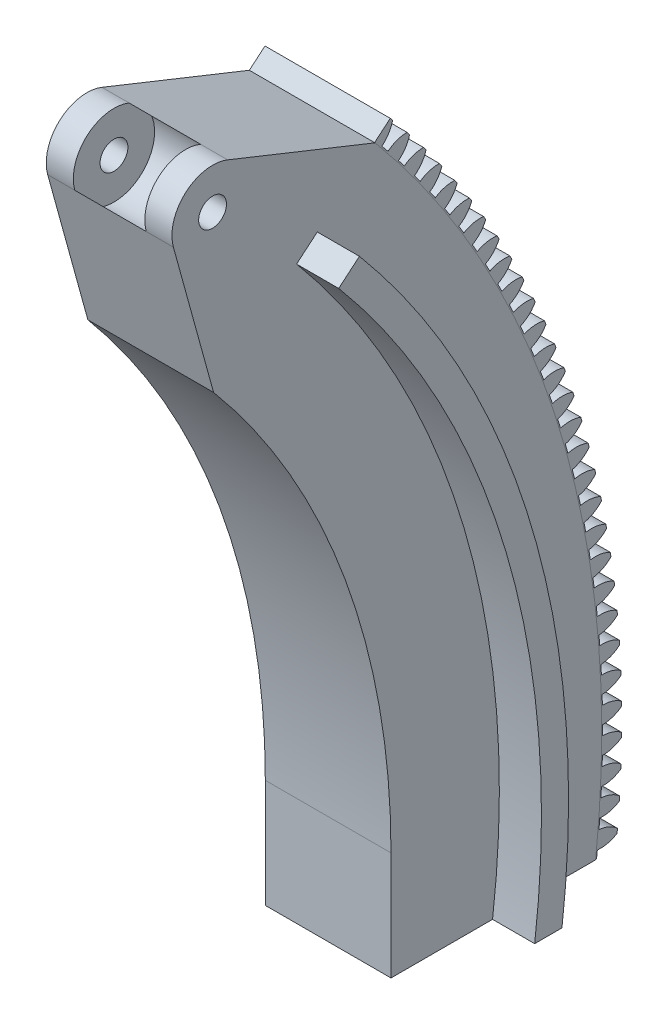
SolidWorks part; units mm, degrees
material "ABS"
ref_plane "Front Plane" through (0, 0, 0) normal (0, 0, 1) x (1, 0, 0)
ref_plane "Top Plane" through (0, 0, 0) normal (0, 1, 0) x (1, 0, 0)
ref_plane "Right Plane" through (0, 0, 0) normal (1, 0, 0) x (0, 0, -1)
ref_plane "Plane2" through (6.35, 0, 0) normal (1, 0, 0) x (0, 0, -1)
sketch "Sketch1" plane through (0, 0, 0) normal (1, 0, 0) x (0, 0, -1)
  line L0 (-1000, 0) -> (177.8, 0) construction
  line L1 (177.8, 0) -> (177.8, -25.4)
  line L2 (0, 0) -> (136.2027, 114.2876) construction
  line L4 (227.2, 0) -> (49000, 0) construction
  line L7 (177.8, -25.4) -> (227.2, -25.4) construction
  line L8 (227.2, 0) -> (227.2, -25.4) construction
  line L10 (-1.0719, -0.8495) -> (179.1555, 141.9904) construction
  line L61 (181.0098, 139.6187) -> (0, 0) construction
  line L62 (136.2027, 114.2876) -> (126.7844, 148.4774)
  line L64 (177.8, -25.4) -> (225.7757, -25.4)
  line L65 (136.2027, 114.2876) -> (155.124, 130.1645) construction
  line L66 (155.124, 130.1645) -> (174.0453, 146.0413) construction
  line L68 (0, 0) -> (35966.99, 34732.9185) construction
  line L69 (178.0587, 141.1212) -> (178.0836, 141.1409) construction
  line L70 (0, 0) -> (135.9673, 151.007) construction
  line L71 (139.5033, 159.8514) -> (174.0453, 146.0413)
  arc A2 (177.8, 0) -> (136.2027, 114.2876) centre (0, 0) ccw
  circle A19 centre (0, 0) radius 228.6 construction
  arc A22 (174.0453, 146.0413) -> (227.2, 0) centre (0, 0) cw
  arc A23 (227.2, 0) -> (225.7757, -25.4) centre (0, 0) cw
  arc A24 (126.7844, 148.4774) -> (139.5033, 159.8514) centre (135.9673, 151.007) cw
  point P6 (178.0836, 141.1409)
  point P7 (136.2027, 114.2876)
  dimension "D1" = 177.8
  dimension "D2" = 6.35
  dimension "D12" = 457.2
  dimension "D8" = 9.525
  dimension "D3" = 40
  dimension "D4" = 49.4
  dimension "D5" = 25.4
  dimension "D6" = 203.2
  dimension "D7" = 48
  dimension "D13" = 44
sketch "Sketch2" plane through (6.35, 0, 0) normal (1, 0, 0) x (0, 0, -1)
  line L0 (0, 0) -> (165.1, 0) construction
  line L1 (165.1, 0) -> (190.5, 0) construction
  line L2 (0, 0) -> (49240.3877, 8682.4089) construction
  circle A0 centre (165.1, 0) radius 3.2639
  circle A1 centre (190.5, 0) radius 3.2639
  arc A3 (165.1, 0) -> (162.5918, 28.6693) centre (0, 0) ccw construction
  circle A4 centre (162.5918, 28.6693) radius 3.2639
  arc A5 (190.5, 0) -> (187.6059, 33.08) centre (0, 0) ccw construction
  circle A6 centre (187.6059, 33.08) radius 3.2639
  dimension "D3" = 6.5278
  dimension "D4" = 6.5278
  dimension "D6" = 6.5278
  dimension "D7" = 6.5278
  dimension "D1" = 165.1
  dimension "D2" = 25.4
  dimension "D5" = 10
sketch "Sketch11" plane through (6.35, 0, 0) normal (1, 0, 0) x (0, 0, -1)
  line L0 (-785.502, -659.1144) -> (0, 0) construction
  line L2 (-1000, 0) -> (0, 0) construction
  line L4 (155.6602, 130.6144) -> (177.7223, 149.1267)
  line L5 (177.7223, 149.1267) -> (921.7047, 773.4021) construction
  line L6 (232, 0) -> (232, -25.4) construction
  line L7 (232, -25.4) -> (222.9391, -25.4) construction
  line L8 (201.6062, -25.4) -> (230.6054, -25.4)
  line L9 (203.2, 0) -> (232, 0) construction
  arc A0 (-230, 0) -> (-176.1902, -147.8412) centre (0, 0) ccw construction
  arc A1 (-232, 0) -> (-177.7223, -149.1267) centre (0, 0) ccw construction
  arc A2 (-229.6, 0) -> (-175.8838, -147.584) centre (0, 0) ccw construction
  arc A3 (232, 0) -> (177.7223, 149.1267) centre (0, 0) ccw
  arc A4 (230, 0) -> (176.1902, 147.8412) centre (0, 0) ccw construction
  arc A5 (-229.6, 0) -> (-175.8838, -147.584) centre (0, 0) ccw
  arc A6 (155.6602, 130.6144) -> (203.2, 0) centre (0, 0) cw
  arc A7 (232, 0) -> (230.6054, -25.4) centre (0, 0) cw
  arc A8 (203.2, 0) -> (201.6062, -25.4) centre (0, 0) cw
  dimension "D1" = 460
  dimension "D2" = 464
  dimension "D4" = 203.2
  dimension "D3" = 2.4
  dimension "D6" = 25.4
extrude "Boss-Extrude2" add sketch "Sketch11" against normal blind 6.35 contours A3 L4 region at (6.35, 60.7212, -203.0048)
sketch "Sketch12" plane through (6.35, 0, 0) normal (1, 0, 0) x (0, 0, -1)
  line L0 (0, 0) -> (232, 0) construction
  line L2 (229.9946, 1.5708) -> (229.9946, -1.5708) construction
  line L3 (0, 0) -> (227.4972, 1.1241) construction
  line L4 (225.6789, 0) -> (232.9848, 2.6591) construction
  line L5 (0, 0) -> (232.9783, 3.1825) construction
  line L6 (229.9946, 1.5708) -> (229.9517, 4.7121) construction
  circle A0 centre (0, 0) radius 230 construction
  arc A1 (230.6054, -25.4) -> (177.7223, 149.1267) centre (0, 0) ccw construction
  circle A2 centre (0, 0) radius 227.5 construction
  arc A3 (227.4972, 1.1241) -> (232.9725, 3.5819) centre (227.4606, 8.5329) ccw
  arc A4 (231.5994, -25.5095) -> (232.9725, -3.5819) centre (0, 0) cw construction
  arc A5 (227.4972, -1.1241) -> (232.9725, -3.5819) centre (227.4606, -8.5329) cw
  arc A6 (231.5994, -25.5095) -> (178.4884, 149.7695) centre (0, 0) ccw
  arc A7 (231.5994, -25.5095) -> (232.9725, 3.5819) centre (0, 0) ccw construction
  arc A8 (227.4972, 1.1241) -> (227.4972, -1.1241) centre (0, 0) cw
  arc A9 (230.6054, -25.4) -> (177.7223, 149.1267) centre (0, 0) ccw construction
  arc A10 (232.9725, 3.5819) -> (232.9725, -3.5819) centre (0, 0) cw
  dimension "D1" = 460
  dimension "D3" = 20
  dimension "D4" = 0.783
  dimension "D5" = 4.5
  dimension "D2" = 1
extrude "Boss-Extrude3" add sketch "Sketch1" along normal blind 29.464
extrude "Cut-Extrude4" cut sketch "Sketch12" against normal blind 6.35
pattern_circular "CirPattern3" count 230 every 1.565 about axis through (0, 0, 0) along (1, 0, 0) of "Cut-Extrude4"
sketch "Sketch15" plane through (6.35, 0, 0) normal (1, 0, 0) x (0, 0, -1)
  line L0 (0, 0) -> (135.9673, 151.007) construction
  line L2 (0, 0) -> (102.4673, 0) construction
  circle A0 centre (135.9673, 151.007) radius 3.2639
  dimension "D3" = 6.5278
  dimension "D1" = 203.2
  dimension "D2" = 48
extrude "Cut-Extrude7" cut sketch "Sketch15" against normal through all both and the other way through all
sketch "Sketch22" plane through (6.35, 0, 0) normal (1, 0, 0) x (0, 0, -1)
  line L0 (0, 0) -> (135.9673, 151.007)
  line L1 (0, 0) -> (177.8, 0)
  dimension "D1" = 177.8
sketch "Sketch23" plane through (0, 0, 0) normal (1, 0, 0) x (0, 0, -1)
  line L0 (0, 0) -> (177.8, 0) construction
  line L1 (0, 0) -> (136.2027, 114.2876) construction
  line L2 (177.8, 0) -> (196.85, 0) construction
  line L3 (136.2027, 114.2876) -> (155.6602, 130.6144) construction
  line L5 (155.6602, 130.6144) -> (160.5246, 134.6961)
  line L7 (201.6062, -25.4) -> (0, 0) construction
  line L8 (208.0049, -25.4) -> (201.6062, -25.4)
  line L9 (177.8, -25.4) -> (226.0776, -25.4) construction
  arc A0 (177.8, 0) -> (136.2027, 114.2876) centre (0, 0) ccw construction
  circle A2 centre (196.85, 0) radius 6.35 construction
  arc A3 (203.2, 0) -> (155.6602, 130.6144) centre (0, 0) ccw
  arc A4 (209.55, 0) -> (160.5246, 134.6961) centre (0, 0) ccw
  circle A5 centre (215.9, 0) radius 6.35 construction
  arc A6 (203.2, 0) -> (201.6062, -25.4) centre (0, 0) cw
  arc A7 (209.55, 0) -> (208.0049, -25.4) centre (0, 0) cw
  dimension "D4" = 6.35
  dimension "D5" = 12.7
  dimension "D6" = 12.7
  dimension "D1" = 177.8
  dimension "D2" = 40
  dimension "D3" = 19.05
extrude "Boss-Extrude4" add sketch "Sketch23" against normal blind 9.8742
ref_plane "Plane3" through (14.732, 0, 0) normal (1, 0, 0) x (0, 0, -1)
mirror "Mirror2" about plane through (14.732, 0, 0) normal (1, 0, 0) of "Boss-Extrude4"
sketch "Sketch27" plane through (6.35, 0, 0) normal (1, 0, 0) x (0, 0, -1)
  line L2 (177.7223, 149.1267) -> (174.0453, 146.0413)
  line L3 (177.7223, 149.1267) -> (174.0453, 146.0413)
  line L7 (225.7757, -25.4) -> (226.0776, -25.4)
  line L8 (225.7757, -25.4) -> (226.0776, -25.4)
  arc A4 (227.2191, 11.3011) -> (227.0964, 13.5458) centre (0, 0) ccw
  arc A95 (231.8253, 9.0012) -> (231.7841, 10.0069) centre (0, 0) ccw
  arc A111 (227.3816, 7.3377) -> (231.8253, 9.0012) centre (227.1427, 14.7428) ccw
  arc A112 (227.3816, 7.3377) -> (231.8253, 9.0012) centre (227.1427, 14.7428) ccw
  arc A113 (231.7841, 10.0069) -> (227.2191, 11.3011) centre (227.5872, 3.9012) ccw
  arc A114 (231.7841, 10.0069) -> (227.2191, 11.3011) centre (227.5872, 3.9012) ccw
  arc A139 (227.2191, 11.3011) -> (227.0964, 13.5458) centre (0, 0) ccw
  arc A141 (227.0964, 13.5458) -> (231.493, 15.3301) centre (226.6552, 20.9417) ccw
  arc A143 (227.0964, 13.5458) -> (231.493, 15.3301) centre (226.6552, 20.9417) ccw
  arc A145 (231.493, 15.3301) -> (231.4243, 16.3343) centre (0, 0) ccw
  arc A147 (231.493, 15.3301) -> (231.4243, 16.3343) centre (0, 0) ccw
  arc A149 (231.4243, 16.3343) -> (226.8257, 17.5033) centre (227.3957, 10.1163) ccw
  arc A151 (231.4243, 16.3343) -> (226.8257, 17.5033) centre (227.3957, 10.1163) ccw
  arc A153 (226.8257, 17.5033) -> (226.6416, 19.7439) centre (0, 0) ccw
  arc A155 (226.8257, 17.5033) -> (226.6416, 19.7439) centre (0, 0) ccw
  arc A157 (226.6416, 19.7439) -> (230.9878, 21.6476) centre (225.9986, 27.1249) ccw
  arc A159 (226.6416, 19.7439) -> (230.9878, 21.6476) centre (225.9986, 27.1249) ccw
  arc A161 (230.9878, 21.6476) -> (230.8918, 22.6495) centre (0, 0) ccw
  arc A163 (230.9878, 21.6476) -> (230.8918, 22.6495) centre (0, 0) ccw
  arc A165 (230.8918, 22.6495) -> (226.2629, 23.6925) centre (227.0345, 16.3238) ccw
  arc A167 (230.8918, 22.6495) -> (226.2629, 23.6925) centre (227.0345, 16.3238) ccw
  arc A169 (226.2629, 23.6925) -> (226.0178, 25.9272) centre (0, 0) ccw
  arc A171 (226.2629, 23.6925) -> (226.0178, 25.9272) centre (0, 0) ccw
  arc A173 (226.0178, 25.9272) -> (230.3104, 27.9489) centre (225.1734, 33.2879) ccw
  arc A175 (226.0178, 25.9272) -> (230.3104, 27.9489) centre (225.1734, 33.2879) ccw
  arc A177 (230.3104, 27.9489) -> (230.1869, 28.9478) centre (0, 0) ccw
  arc A179 (230.3104, 27.9489) -> (230.1869, 28.9478) centre (0, 0) ccw
  arc A181 (230.1869, 28.9478) -> (225.5314, 29.8639) centre (226.5039, 22.5191) ccw
  arc A182 (230.1869, 28.9478) -> (225.5314, 29.8639) centre (226.5039, 22.5191) ccw
  arc A184 (225.5314, 29.8639) -> (225.2252, 32.0911) centre (0, 0) ccw
  arc A186 (225.5314, 29.8639) -> (225.2252, 32.0911) centre (0, 0) ccw
  arc A189 (231.8253, 9.0012) -> (231.7841, 10.0069) centre (0, 0) ccw
  arc A282 (225.2252, 32.0911) -> (229.461, 34.2294) centre (224.1801, 39.426) ccw
  arc A284 (225.2252, 32.0911) -> (229.461, 34.2294) centre (224.1801, 39.426) ccw
  arc A286 (229.461, 34.2294) -> (229.3104, 35.2245) centre (0, 0) ccw
  arc A288 (229.461, 34.2294) -> (229.3104, 35.2245) centre (0, 0) ccw
  arc A290 (229.3104, 35.2245) -> (224.6315, 36.0131) centre (225.8043, 28.6976) ccw
  arc A292 (229.3104, 35.2245) -> (224.6315, 36.0131) centre (225.8043, 28.6976) ccw
  arc A294 (224.6315, 36.0131) -> (224.2647, 38.2311) centre (0, 0) ccw
  arc A296 (224.6315, 36.0131) -> (224.2647, 38.2311) centre (0, 0) ccw
  arc A298 (224.2647, 38.2311) -> (228.4404, 40.4843) centre (223.0196, 45.5347) ccw
  arc A300 (224.2647, 38.2311) -> (228.4404, 40.4843) centre (223.0196, 45.5347) ccw
  arc A302 (228.4404, 40.4843) -> (228.2626, 41.4749) centre (0, 0) ccw
  arc A304 (228.4404, 40.4843) -> (228.2626, 41.4749) centre (0, 0) ccw
  arc A306 (228.2626, 41.4749) -> (223.564, 42.1355) centre (224.9362, 34.8547) ccw
  arc A308 (228.2626, 41.4749) -> (223.564, 42.1355) centre (224.9362, 34.8547) ccw
  arc A310 (223.564, 42.1355) -> (223.1367, 44.3426) centre (0, 0) ccw
  arc A312 (223.564, 42.1355) -> (223.1367, 44.3426) centre (0, 0) ccw
  arc A314 (223.1367, 44.3426) -> (227.2494, 46.709) centre (221.6926, 51.6095) ccw
  arc A316 (223.1367, 44.3426) -> (227.2494, 46.709) centre (221.6926, 51.6095) ccw
  arc A318 (227.2494, 46.709) -> (227.0446, 47.6944) centre (0, 0) ccw
  arc A320 (227.2494, 46.709) -> (227.0446, 47.6944) centre (0, 0) ccw
  arc A322 (227.0446, 47.6944) -> (222.3296, 48.2264) centre (223.9002, 40.9858) ccw
  arc A324 (227.0446, 47.6944) -> (222.3296, 48.2264) centre (223.9002, 40.9858) ccw
  arc A326 (222.3296, 48.2264) -> (221.8422, 50.421) centre (0, 0) ccw
  arc A328 (222.3296, 48.2264) -> (221.8422, 50.421) centre (0, 0) ccw
  arc A330 (221.8422, 50.421) -> (225.8887, 52.8988) centre (220.2002, 57.6457) ccw
  arc A332 (221.8422, 50.421) -> (225.8887, 52.8988) centre (220.2002, 57.6457) ccw
  arc A334 (225.8887, 52.8988) -> (225.6571, 53.8783) centre (0, 0) ccw
  arc A336 (225.8887, 52.8988) -> (225.6571, 53.8783) centre (0, 0) ccw
  arc A338 (225.6571, 53.8783) -> (220.9294, 54.2813) centre (222.6972, 47.0863) ccw
  arc A340 (225.6571, 53.8783) -> (220.9294, 54.2813) centre (222.6972, 47.0863) ccw
  arc A342 (220.9294, 54.2813) -> (220.3822, 56.4618) centre (0, 0) ccw
  arc A344 (220.9294, 54.2813) -> (220.3822, 56.4618) centre (0, 0) ccw
  arc A346 (220.3822, 56.4618) -> (224.3595, 59.0492) centre (218.5434, 63.6389) ccw
  arc A348 (220.3822, 56.4618) -> (224.3595, 59.0492) centre (218.5434, 63.6389) ccw
  arc A350 (224.3595, 59.0492) -> (224.1012, 60.022) centre (0, 0) ccw
  arc A352 (224.3595, 59.0492) -> (224.1012, 60.022) centre (0, 0) ccw
  arc A354 (224.1012, 60.022) -> (219.3643, 60.2956) centre (221.3279, 53.1516) ccw
  arc A356 (224.1012, 60.022) -> (219.3643, 60.2956) centre (221.3279, 53.1516) ccw
  arc A358 (219.3643, 60.2956) -> (218.7577, 62.4604) centre (0, 0) ccw
  arc A360 (219.3643, 60.2956) -> (218.7577, 62.4604) centre (0, 0) ccw
  arc A362 (218.7577, 62.4604) -> (222.6629, 65.1555) centre (216.7236, 69.5847) ccw
  arc A364 (218.7577, 62.4604) -> (222.6629, 65.1555) centre (216.7236, 69.5847) ccw
  arc A366 (222.6629, 65.1555) -> (222.3781, 66.1209) centre (0, 0) ccw
  arc A368 (222.6629, 65.1555) -> (222.3781, 66.1209) centre (0, 0) ccw
  arc A370 (222.3781, 66.1209) -> (217.6355, 66.265) centre (219.7935, 59.1773) ccw
  arc A372 (222.3781, 66.1209) -> (217.6355, 66.265) centre (219.7935, 59.1773) ccw
  arc A374 (217.6355, 66.265) -> (216.97, 68.4124) centre (0, 0) ccw
  arc A376 (217.6355, 66.265) -> (216.97, 68.4124) centre (0, 0) ccw
  arc A378 (216.97, 68.4124) -> (220.8001, 71.2132) centre (214.742, 75.4785) ccw
  arc A380 (216.97, 68.4124) -> (220.8001, 71.2132) centre (214.742, 75.4785) ccw
  arc A382 (220.8001, 71.2132) -> (220.4891, 72.1704) centre (0, 0) ccw
  arc A384 (220.8001, 71.2132) -> (220.4891, 72.1704) centre (0, 0) ccw
  arc A386 (220.4891, 72.1704) -> (215.7443, 72.185) centre (218.0951, 65.1589) ccw
  arc A388 (220.4891, 72.1704) -> (215.7443, 72.185) centre (218.0951, 65.1589) ccw
  arc A390 (215.7443, 72.185) -> (215.0204, 74.3134) centre (0, 0) ccw
  arc A394 (215.7443, 72.185) -> (215.0204, 74.3134) centre (0, 0) ccw
  arc A398 (215.0204, 74.3134) -> (218.7726, 77.2177) centre (212.6002, 81.3159) ccw
  arc A402 (215.0204, 74.3134) -> (218.7726, 77.2177) centre (212.6002, 81.3159) ccw
  arc A406 (218.7726, 77.2177) -> (218.4355, 78.1661) centre (0, 0) ccw
  arc A410 (218.7726, 77.2177) -> (218.4355, 78.1661) centre (0, 0) ccw
  arc A414 (218.4355, 78.1661) -> (213.692, 78.0511) centre (216.2339, 71.0918) ccw
  arc A418 (218.4355, 78.1661) -> (213.692, 78.0511) centre (216.2339, 71.0918) ccw
  arc A420 (213.692, 78.0511) -> (212.9103, 80.1589) centre (0, 0) ccw
  arc A422 (213.692, 78.0511) -> (212.9103, 80.1589) centre (0, 0) ccw
  arc A423 (212.9103, 80.1589) -> (216.5817, 83.1646) centre (210.2998, 87.0927) ccw
  arc A424 (212.9103, 80.1589) -> (216.5817, 83.1646) centre (210.2998, 87.0927) ccw
  arc A425 (216.5817, 83.1646) -> (216.2189, 84.1034) centre (0, 0) ccw
  arc A426 (216.5817, 83.1646) -> (216.2189, 84.1034) centre (0, 0) ccw
  arc A427 (216.2189, 84.1034) -> (211.4804, 83.8589) centre (214.2114, 76.9716) ccw
  arc A428 (216.2189, 84.1034) -> (211.4804, 83.8589) centre (214.2114, 76.9716) ccw
  arc A429 (211.4804, 83.8589) -> (210.6414, 85.9446) centre (0, 0) ccw
  arc A430 (211.4804, 83.8589) -> (210.6414, 85.9446) centre (0, 0) ccw
  arc A431 (210.6414, 85.9446) -> (214.2293, 89.0495) centre (207.8424, 92.8045) ccw
  arc A432 (210.6414, 85.9446) -> (214.2293, 89.0495) centre (207.8424, 92.8045) ccw
  arc A434 (214.2293, 89.0495) -> (213.841, 89.978) centre (0, 0) ccw
  arc A436 (214.2293, 89.0495) -> (213.841, 89.978) centre (0, 0) ccw
  arc A438 (213.841, 89.978) -> (209.1109, 89.6041) centre (212.029, 82.794) ccw
  arc A440 (213.841, 89.978) -> (209.1109, 89.6041) centre (212.029, 82.794) ccw
  arc A442 (209.1109, 89.6041) -> (208.2152, 91.6661) centre (0, 0) ccw
  arc A444 (209.1109, 89.6041) -> (208.2152, 91.6661) centre (0, 0) ccw
  arc A446 (208.2152, 91.6661) -> (211.717, 94.8679) centre (205.2299, 98.4471) ccw
  arc A448 (208.2152, 91.6661) -> (211.717, 94.8679) centre (205.2299, 98.4471) ccw
  arc A450 (211.717, 94.8679) -> (211.3034, 95.7855) centre (0, 0) ccw
  arc A452 (211.717, 94.8679) -> (211.3034, 95.7855) centre (0, 0) ccw
  arc A454 (211.3034, 95.7855) -> (206.5853, 95.2825) centre (209.6884, 88.5547) ccw
  arc A456 (211.3034, 95.7855) -> (206.5853, 95.2825) centre (209.6884, 88.5547) ccw
  arc A458 (206.5853, 95.2825) -> (205.6337, 97.3193) centre (0, 0) ccw
  arc A460 (206.5853, 95.2825) -> (205.6337, 97.3193) centre (0, 0) ccw
  arc A462 (205.6337, 97.3193) -> (209.0467, 100.6155) centre (202.4643, 104.0162) ccw
  arc A464 (205.6337, 97.3193) -> (209.0467, 100.6155) centre (202.4643, 104.0162) ccw
  arc A466 (209.0467, 100.6155) -> (208.6082, 101.5215) centre (0, 0) ccw
  arc A467 (209.0467, 100.6155) -> (208.6082, 101.5215) centre (0, 0) ccw
  arc A468 (208.6082, 101.5215) -> (203.9056, 100.8898) centre (207.1913, 94.2492) ccw
  arc A469 (208.6082, 101.5215) -> (203.9056, 100.8898) centre (207.1913, 94.2492) ccw
  arc A470 (203.9056, 100.8898) -> (202.8987, 102.8998) centre (0, 0) ccw
  arc A471 (203.9056, 100.8898) -> (202.8987, 102.8998) centre (0, 0) ccw
  arc A472 (202.8987, 102.8998) -> (206.2204, 106.288) centre (199.5476, 109.5076) ccw
  arc A473 (202.8987, 102.8998) -> (206.2204, 106.288) centre (199.5476, 109.5076) ccw
  arc A474 (206.2204, 106.288) -> (205.7574, 107.1817) centre (0, 0) ccw
  arc A475 (206.2204, 106.288) -> (205.7574, 107.1817) centre (0, 0) ccw
  arc A476 (205.7574, 107.1817) -> (201.0737, 106.4218) centre (204.5396, 99.8735) ccw
  arc A477 (205.7574, 107.1817) -> (201.0737, 106.4218) centre (204.5396, 99.8735) ccw
  arc A478 (201.0737, 106.4218) -> (200.0123, 108.4036) centre (0, 0) ccw
  arc A479 (201.0737, 106.4218) -> (200.0123, 108.4036) centre (0, 0) ccw
  arc A480 (200.0123, 108.4036) -> (203.2402, 111.8812) centre (196.4819, 114.9174) ccw
  arc A481 (200.0123, 108.4036) -> (203.2402, 111.8812) centre (196.4819, 114.9174) ccw
  arc A482 (203.2402, 111.8812) -> (202.7529, 112.7619) centre (0, 0) ccw
  arc A483 (203.2402, 111.8812) -> (202.7529, 112.7619) centre (0, 0) ccw
  arc A484 (202.7529, 112.7619) -> (198.0918, 111.8744) centre (201.7352, 105.4232) ccw
  arc A485 (202.7529, 112.7619) -> (198.0918, 111.8744) centre (201.7352, 105.4232) ccw
  arc A486 (198.0918, 111.8744) -> (196.9766, 113.8264) centre (0, 0) ccw
  arc A487 (198.0918, 111.8744) -> (196.9766, 113.8264) centre (0, 0) ccw
  arc A488 (196.9766, 113.8264) -> (200.1084, 117.3909) centre (193.2697, 120.2413) ccw
  arc A489 (196.9766, 113.8264) -> (200.1084, 117.3909) centre (193.2697, 120.2413) ccw
  arc A490 (200.1084, 117.3909) -> (199.5972, 118.258) centre (0, 0) ccw
  arc A491 (200.1084, 117.3909) -> (199.5972, 118.258) centre (0, 0) ccw
  arc A492 (199.5972, 118.258) -> (194.9621, 117.2435) centre (198.7804, 110.8942) ccw
  arc A493 (199.5972, 118.258) -> (194.9621, 117.2435) centre (198.7804, 110.8942) ccw
  arc A494 (194.9621, 117.2435) -> (193.794, 119.1643) centre (0, 0) ccw
  arc A495 (194.9621, 117.2435) -> (193.794, 119.1643) centre (0, 0) ccw
  arc A496 (193.794, 119.1643) -> (196.8272, 122.8131) centre (189.9132, 125.4756) ccw
  arc A497 (193.794, 119.1643) -> (196.8272, 122.8131) centre (189.9132, 125.4756) ccw
  arc A498 (196.8272, 122.8131) -> (196.2926, 123.6658) centre (0, 0) ccw
  arc A499 (196.8272, 122.8131) -> (196.2926, 123.6658) centre (0, 0) ccw
  arc A500 (196.2926, 123.6658) -> (191.6869, 122.5251) centre (195.6771, 116.2824) ccw
  arc A501 (196.2926, 123.6658) -> (191.6869, 122.5251) centre (195.6771, 116.2824) ccw
  arc A502 (191.6869, 122.5251) -> (190.4667, 124.4133) centre (0, 0) ccw
  arc A503 (191.6869, 122.5251) -> (190.4667, 124.4133) centre (0, 0) ccw
  arc A504 (190.4667, 124.4133) -> (193.3992, 128.1435) centre (186.415, 130.6162) ccw
  arc A505 (190.4667, 124.4133) -> (193.3992, 128.1435) centre (186.415, 130.6162) ccw
  arc A506 (193.3992, 128.1435) -> (192.8414, 128.9814) centre (0, 0) ccw
  arc A507 (193.3992, 128.1435) -> (192.8414, 128.9814) centre (0, 0) ccw
  arc A508 (192.8414, 128.9814) -> (188.2686, 127.7153) centre (192.4279, 121.5839) ccw
  arc A509 (192.8414, 128.9814) -> (188.2686, 127.7153) centre (192.4279, 121.5839) ccw
  arc A510 (188.2686, 127.7153) -> (186.9974, 129.5694) centre (0, 0) ccw
  arc A511 (188.2686, 127.7153) -> (186.9974, 129.5694) centre (0, 0) ccw
  arc A512 (186.9974, 129.5694) -> (189.8268, 133.3784) centre (182.7777, 135.6594) ccw
  arc A513 (186.9974, 129.5694) -> (189.8268, 133.3784) centre (182.7777, 135.6594) ccw
  arc A514 (189.8268, 133.3784) -> (189.2464, 134.2007) centre (0, 0) ccw
  arc A515 (189.8268, 133.3784) -> (189.2464, 134.2007) centre (0, 0) ccw
  arc A516 (189.2464, 134.2007) -> (184.7098, 132.8101) centre (189.0351, 126.7947) ccw
  arc A517 (189.2464, 134.2007) -> (184.7098, 132.8101) centre (189.0351, 126.7947) ccw
  arc A518 (184.7098, 132.8101) -> (183.3884, 134.6289) centre (0, 0) ccw
  arc A519 (184.7098, 132.8101) -> (183.3884, 134.6289) centre (0, 0) ccw
  arc A520 (225.7757, -25.4) -> (174.0453, 146.0413) centre (0, 0) ccw
  arc A521 (225.7757, -25.4) -> (174.0453, 146.0413) centre (0, 0) ccw
  arc A522 (227.4972, -1.1241) -> (227.4972, 1.1241) centre (0, 0) ccw
  arc A523 (227.4972, -1.1241) -> (227.4972, 1.1241) centre (0, 0) ccw
  arc A524 (227.4972, 1.1241) -> (231.9847, 2.6656) centre (227.4606, 8.5329) ccw
  arc A525 (227.4972, 1.1241) -> (231.9847, 2.6656) centre (227.4606, 8.5329) ccw
  arc A526 (231.9847, 2.6656) -> (231.9709, 3.672) centre (0, 0) ccw
  arc A527 (231.9847, 2.6656) -> (231.9709, 3.672) centre (0, 0) ccw
  arc A528 (231.9709, 3.672) -> (227.4431, 5.0904) centre (227.6088, -2.3167) ccw
  arc A529 (231.9709, 3.672) -> (227.4431, 5.0904) centre (227.6088, -2.3167) ccw
  arc A530 (227.4431, 5.0904) -> (227.3816, 7.3377) centre (0, 0) ccw
  arc A531 (227.4431, 5.0904) -> (227.3816, 7.3377) centre (0, 0) ccw
  arc A532 (231.9709, -3.672) -> (231.9847, -2.6656) centre (0, 0) ccw
  arc A533 (231.9709, -3.672) -> (231.9847, -2.6656) centre (0, 0) ccw
  arc A534 (231.9847, -2.6656) -> (227.4972, -1.1241) centre (227.4606, -8.5329) ccw
  arc A535 (231.9847, -2.6656) -> (227.4972, -1.1241) centre (227.4606, -8.5329) ccw
  arc A536 (183.3884, 134.6289) -> (186.1128, 138.5137) centre (179.004, 140.6013) ccw
  arc A537 (183.3884, 134.6289) -> (186.1128, 138.5137) centre (179.004, 140.6013) ccw
  arc A538 (186.1128, 138.5137) -> (185.5101, 139.3198) centre (0, 0) ccw
  arc A539 (186.1128, 138.5137) -> (185.5101, 139.3198) centre (0, 0) ccw
  arc A540 (185.5101, 139.3198) -> (181.0132, 137.8059) centre (185.5011, 131.9108) ccw
  arc A541 (185.5101, 139.3198) -> (181.0132, 137.8059) centre (185.5011, 131.9108) ccw
  arc A542 (181.0132, 137.8059) -> (179.6426, 139.5879) centre (0, 0) ccw
  arc A543 (181.0132, 137.8059) -> (179.6426, 139.5879) centre (0, 0) ccw
  arc A544 (179.6426, 139.5879) -> (182.2598, 143.5456) centre (175.0967, 145.4383) ccw
  arc A545 (179.6426, 139.5879) -> (182.2598, 143.5456) centre (175.0967, 145.4383) ccw
  arc A546 (182.2598, 143.5456) -> (181.6354, 144.335) centre (0, 0) ccw
  arc A547 (182.2598, 143.5456) -> (181.6354, 144.335) centre (0, 0) ccw
  arc A548 (181.6354, 144.335) -> (177.1815, 142.6988) centre (181.8288, 136.9286) ccw
  arc A549 (181.6354, 144.335) -> (177.1815, 142.6988) centre (181.8288, 136.9286) ccw
  arc A550 (177.1815, 142.6988) -> (175.7628, 144.4427) centre (0, 0) ccw
  arc A551 (177.1815, 142.6988) -> (175.7628, 144.4427) centre (0, 0) ccw
  arc A552 (175.7628, 144.4427) -> (178.2709, 148.4705) centre (171.0587, 150.1668) ccw
  arc A553 (175.7628, 144.4427) -> (178.2709, 148.4705) centre (171.0587, 150.1668) ccw
  arc A554 (178.2709, 148.4705) -> (177.7223, 149.1267) centre (0, 0) ccw
  arc A555 (178.2709, 148.4705) -> (177.7223, 149.1267) centre (0, 0) ccw
  arc A556 (226.0776, -25.4) -> (226.2629, -23.6925) centre (0, 0) ccw
  arc A557 (226.0776, -25.4) -> (226.2629, -23.6925) centre (0, 0) ccw
  arc A558 (226.2629, -23.6925) -> (230.8918, -22.6495) centre (227.0345, -16.3238) ccw
  arc A559 (226.2629, -23.6925) -> (230.8918, -22.6495) centre (227.0345, -16.3238) ccw
  arc A560 (230.8918, -22.6495) -> (230.9878, -21.6476) centre (0, 0) ccw
  arc A561 (230.8918, -22.6495) -> (230.9878, -21.6476) centre (0, 0) ccw
  arc A562 (230.9878, -21.6476) -> (226.6416, -19.7439) centre (225.9986, -27.1249) ccw
  arc A563 (230.9878, -21.6476) -> (226.6416, -19.7439) centre (225.9986, -27.1249) ccw
  arc A564 (226.6416, -19.7439) -> (226.8257, -17.5033) centre (0, 0) ccw
  arc A565 (226.6416, -19.7439) -> (226.8257, -17.5033) centre (0, 0) ccw
  arc A566 (226.8257, -17.5033) -> (231.4243, -16.3343) centre (227.3957, -10.1163) ccw
  arc A567 (226.8257, -17.5033) -> (231.4243, -16.3343) centre (227.3957, -10.1163) ccw
  arc A568 (231.4243, -16.3343) -> (231.493, -15.3301) centre (0, 0) ccw
  arc A569 (231.4243, -16.3343) -> (231.493, -15.3301) centre (0, 0) ccw
  arc A570 (231.493, -15.3301) -> (227.0964, -13.5458) centre (226.6552, -20.9417) ccw
  arc A571 (231.493, -15.3301) -> (227.0964, -13.5458) centre (226.6552, -20.9417) ccw
  arc A572 (227.0964, -13.5458) -> (227.2191, -11.3011) centre (0, 0) ccw
  arc A573 (227.0964, -13.5458) -> (227.2191, -11.3011) centre (0, 0) ccw
  arc A574 (227.2191, -11.3011) -> (231.7841, -10.0069) centre (227.5872, -3.9012) ccw
  arc A575 (227.2191, -11.3011) -> (231.7841, -10.0069) centre (227.5872, -3.9012) ccw
  arc A576 (231.7841, -10.0069) -> (231.8253, -9.0012) centre (0, 0) ccw
  arc A577 (231.7841, -10.0069) -> (231.8253, -9.0012) centre (0, 0) ccw
  arc A578 (231.8253, -9.0012) -> (227.3816, -7.3377) centre (227.1427, -14.7428) ccw
  arc A579 (231.8253, -9.0012) -> (227.3816, -7.3377) centre (227.1427, -14.7428) ccw
  arc A580 (227.3816, -7.3377) -> (227.4431, -5.0904) centre (0, 0) ccw
  arc A581 (227.3816, -7.3377) -> (227.4431, -5.0904) centre (0, 0) ccw
  arc A582 (227.4431, -5.0904) -> (231.9709, -3.672) centre (227.6088, 2.3167) ccw
  arc A583 (227.4431, -5.0904) -> (231.9709, -3.672) centre (227.6088, 2.3167) ccw
  dimension "D1" = 0
extrude "Boss-Extrude6" add sketch "Sketch27" along normal blind 23.0187
ref_plane "Plane4" through (6.35, 0, 0) normal (-1, 0, 0) x (0, 0, 1)
sketch "Sketch28" plane through (6.35, 0, 0) normal (1, 0, 0) x (0, 0, -1)
  circle A0 centre (135.9673, 151.007) radius 9.525
  arc A1 (139.5033, 159.8514) -> (126.7844, 148.4774) centre (135.9673, 151.007) ccw construction
extrude "Cut-Extrude8" cut sketch "Sketch28" along normal blind 16.764
equation "\"Module\"= 2mm"
equation "\"Number of Teeth\"= 230"
equation "\"D1@Sketch12\"=\"Module\" * \"Number of Teeth\""
equation "\"D4@Sketch12\"=180 / \"Number of Teeth\""
equation "\"D2\"= 360 / \"Number of Teeth\""
equation "\"D2@Sketch11\"=( \"Number of Teeth\" + 2) * \"Module\""
equation "\"D2@CirPattern3\"= 360 / \"Number of Teeth\""
equation "\"D5@Sketch12\"= 2.25 * \"Module\""
equation "\"D1@CirPattern3\"=\"Number of Teeth\""
